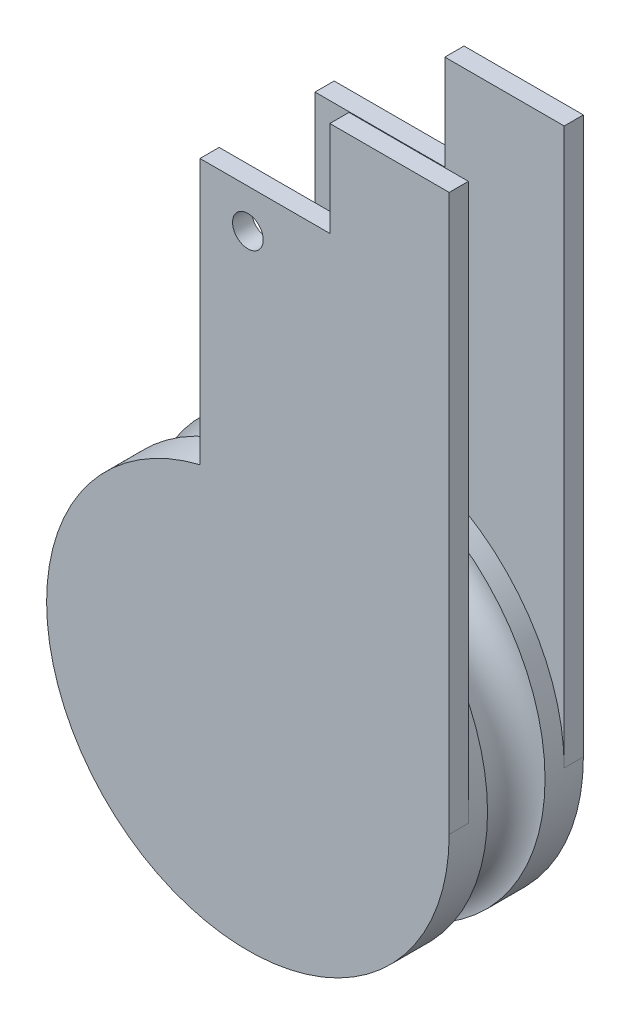
SolidWorks part; units mm, degrees
ref_plane "Front Plane" through (0, 0, 0) normal (0, 0, 1) x (1, 0, 0)
ref_plane "Top Plane" through (0, 0, 0) normal (0, 1, 0) x (1, 0, 0)
ref_plane "Right Plane" through (0, 0, 0) normal (1, 0, 0) x (0, 0, -1)
sketch "Sketch1" plane through (0, 0, 0) normal (0, 0, 1) x (1, 0, 0)
  line L0 (105, 0) -> (105, 290)
  line L1 (105, 290) -> (42.7405, 290)
  line L2 (-25, 240.3304) -> (-25, 101.9804)
  line L3 (-25, 220) -> (105, 220) construction
  line L4 (0, 0) -> (0, 240.3304) construction
  line L5 (-25, 240.3304) -> (42.7405, 240.3304)
  line L6 (42.7405, 240.3304) -> (42.7405, 290)
  circle A0 centre (0, 0) radius 105
  circle A1 centre (0, 220) radius 8
  point P9 (0, 220)
  dimension "D1" = 210
  dimension "D4" = 16
  dimension "D2" = 220
  dimension "D3" = 70
  dimension "D5" = 130
extrude "Boss-Extrude1" add sketch "Sketch1" along normal mid plane 10 contours A0 | A0 L0 L1 L2 A1 region at (49.1632, 175.2544, 0) region at (0, 0, 0)
extrude "Boss-Extrude2" add sketch "Sketch1<3>" along normal blind 50 from surface contours A0 region at (0, 0, 0) starting at face at (23.4456, 171.5062, 5)
sketch "Sketch1<3>" plane through (0, 0, 0) normal (0, 0, 1) x (1, 0, 0) same geometry as "Sketch1"
extrude "Boss-Extrude3" add sketch "Sketch1<4>" along normal blind 10 from surface contours A0 L0 L1 L6 L5 L2 A1 | A0 region at (49.1632, 175.2544, 0) region at (0, 0, 0) starting at face at (105, 0, 55)
sketch "Sketch1<4>" plane through (0, 0, 0) normal (0, 0, 1) x (1, 0, 0) same geometry as "Sketch1"
sketch "Sketch2" plane through (0, 0, 0) normal (1, 0, 0) x (0, 0, -1)
  line L0 (-5, 105) -> (-55, 105) construction
  circle A0 centre (-30, 105) radius 15
ref_axis "Axis1" through (0, 0, 45) along (0, 0, -1)
revolve "Revolve1" add sketch "Sketch2" angle 360 about axis through (0, 0, 45) along (0, 0, -1)
combine bodies "Combine1" operation type subtract main body 103 bodies to subtract 104
ref_plane "Plane1" through (0, 0, 30) normal (0, 0, -1) x (-1, 0, 0)
sketch "Sketch4" plane through (0, 0, 30) normal (0, 0, -1) x (-1, 0, 0)
  circle A0 centre (0, 0) radius 105
